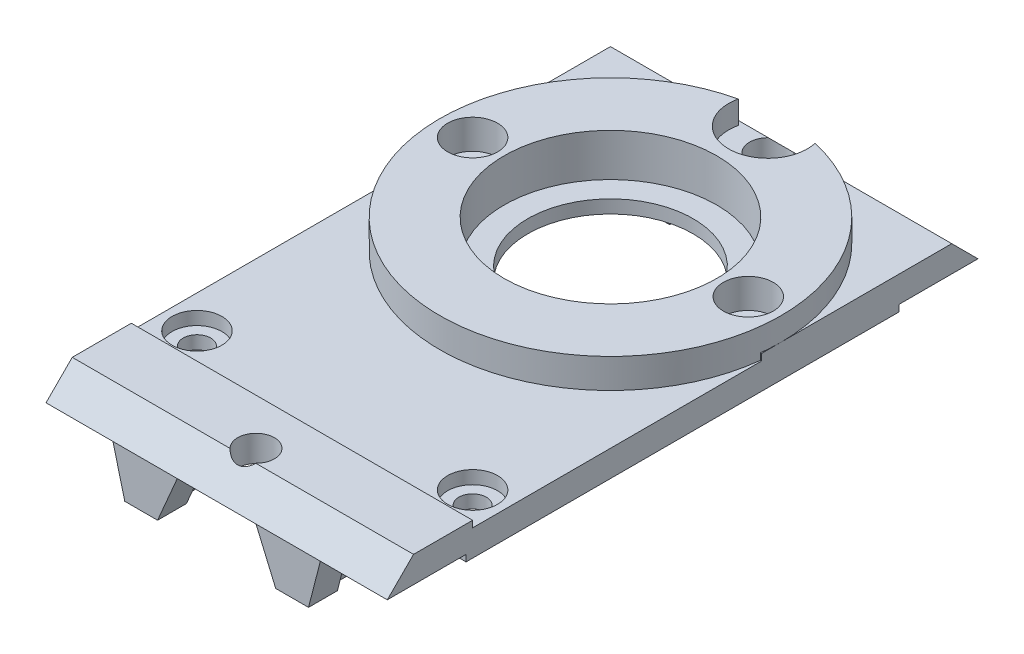
SolidWorks part; units mm, degrees
material "ABS"
ref_plane "正面" through (0, 0, 0) normal (0, 0, 1) x (1, 0, 0)
ref_plane "平面" through (0, 0, 0) normal (0, 1, 0) x (1, 0, 0)
ref_plane "右側面" through (0, 0, 0) normal (1, 0, 0) x (0, 0, -1)
sketch "ｽｹｯﾁ1" plane through (0, 0, 0) normal (0, 1, 0) x (1, 0, 0)
  line L0 (-13, 22.5) -> (13, 22.5)
  line L2 (-13, 22.5) -> (-13, -22.5)
  line L3 (-13, -22.5) -> (13, -22.5)
  line L4 (13, 22.5) -> (13, -22.5)
  line L5 (-13, 22.5) -> (13, -22.5) construction
  line L6 (-13, -22.5) -> (13, 22.5) construction
  point P7 (0, 0)
  dimension "D1" = 0
  dimension "D2" = 0
  dimension "D4" = 45
  dimension "D3" = 26
extrude "ﾎﾞｽ - 押し出し1" add sketch "ｽｹｯﾁ1" along normal blind 2
sketch "ｽｹｯﾁ4" plane through (0, 0, 22.5) normal (0, 0, 1) x (1, 0, 0)
  line L1 (-7, -3.5) -> (-4.5, -3.5)
  line L2 (-4.5, -3.5) -> (-3, 0)
  line L4 (3, 0) -> (4.5, -3.5)
  line L5 (4.5, -3.5) -> (7, -3.5)
  line L8 (7, -3.5) -> (7.9, 0)
  line L10 (-7, -3.5) -> (-7.9, 0)
  line L12 (3, 0) -> (0, 0) construction
  line L13 (0, 0) -> (-3, 0) construction
  line L14 (-7.9, 0) -> (-3, 0)
  line L15 (3, 0) -> (7.9, 0)
  line L16 (-13, 0) -> (13, 0) construction
  dimension "D1" = 7.9
  dimension "D2" = 0
  dimension "D3" = 3
  dimension "D5" = 2.5
  dimension "D6" = 7
  dimension "D9" = 3.5
extrude "ﾎﾞｽ - 押し出し3" add sketch "ｽｹｯﾁ4" against normal blind 6
sketch "ｽｹｯﾁ5" plane through (0, 2, 0) normal (0, 1, 0) x (1, 0, 0)
  line L1 (-13, -22.5) -> (13, -22.5) construction
  circle A0 centre (0, -19.5) radius 1.4
  dimension "D1" = 2.8
  dimension "D2" = 1.4
  dimension "D3" = 3
  dimension "D4" = 0
extrude "ｶｯﾄ - 押し出し1" cut sketch "ｽｹｯﾁ5" against normal up to next
fillet "ﾌｨﾚｯﾄ1" [suppressed] radius 2
sketch "ｽｹｯﾁ6" plane through (13, 0, 0) normal (1, 0, 0) x (0, 0, -1)
  line L1 (-16.5, 0) -> (16.5, 0)
  line L2 (-16.5, 0) -> (-16.5, -0.5)
  line L3 (-16.5, -0.5) -> (16.5, -0.5)
  line L4 (16.5, 0) -> (16.5, -0.5)
  line L5 (-16.5, 0) -> (16.5, -0.5) construction
  line L6 (-16.5, -0.5) -> (16.5, 0) construction
  point P4 (0, -0.25)
  dimension "D1" = 0.5
  dimension "D2" = 33
extrude "ﾎﾞｽ - 押し出し4" add sketch "ｽｹｯﾁ6" against normal up to surface (26 mm away) up to face at (-13, 1, 0)
sketch "ｽｹｯﾁ7" plane through (13, 0, 0) normal (1, 0, 0) x (0, 0, -1)
  line L0 (-22.5, 2) -> (22.5, 2) construction
  line L1 (-16, 2) -> (6, 2)
  line L2 (-16, 2) -> (-16, 1.5)
  line L3 (-16, 1.5) -> (6, 1.5)
  line L4 (6, 2) -> (6, 1.5)
  line L5 (-16, 2) -> (6, 1.5) construction
  line L6 (-16, 1.5) -> (6, 2) construction
  line L8 (-16.5, -3.5) -> (-16.5, -0.5) construction
  point P4 (-5, 1.75)
  dimension "D1" = 0.5
  dimension "D2" = 22
  dimension "D3" = 0.5
extrude "ｶｯﾄ - 押し出し2" cut sketch "ｽｹｯﾁ7" against normal up to next
hole_wizard "M2 丸平ねじ用座ぐり穴1" positions "ｽｹｯﾁ8" profile "ｽｹｯﾁ9" counterbore size "M2" standard "JIS" end condition through all
sketch "ｽｹｯﾁ8" plane through (0, 1.5, 0) normal (0, 1, 0) x (1, 0, 0)
  line L0 (7.7714, -16.5) -> (13, -16.5) construction
  point P0 (10.5, -13.5)
  dimension "D1" = 3
  dimension "D2" = 10.5
sketch "ｽｹｯﾁ9" plane through (10.5, 1.5, 13.5) normal (1, 0, 0) x (0, 0, 1)
  line L0 (0, 0) -> (0, 5)
  line L1 (0, 5) -> (1.05, 5)
  line L3 (1.05, 5) -> (1.05, 1)
  line L4 (1.05, 1) -> (1.9, 1)
  line L5 (1.9, 1) -> (1.9, 0)
  line L7 (1.9, 0) -> (0, 0)
  line L11 (0, -6.35) -> (0, 107.95) construction
  dimension "通し穴の直径" = 2.1
  dimension "通し穴の深さ" = 5
  dimension "座ぐり穴の直径" = 3.8
  dimension "座ぐり穴の深さ" = 1
chamfer "面取り1" distance 2 angle 45 2 edges at (0, 2, 22.5) (0, 2, -22.5)
mirror "ﾐﾗｰ1" about plane through (0, 0, 0) normal (0, 0, 1) of "ｶｯﾄ - 押し出し1", "ﾎﾞｽ - 押し出し3"
sketch "ｽｹｯﾁ11" plane through (0, 1.5, 0) normal (0, 1, 0) x (1, 0, 0)
  line L0 (0, -3.9875) -> (0, 3.9875) construction
  arc A0 (-2.925, 20.1667) -> (2.925, 20.1667) centre (0, 7.5) ccw
  circle A1 centre (10.5, -13.5) radius 1.05 construction
  arc A2 (-2.925, 20.1667) -> (2.925, 20.1667) centre (0, 19.5) ccw
  dimension "D1" = 26
  dimension "D2" = 21
  dimension "D3" = 6
extrude "ﾎﾞｽ - 押し出し5" add sketch "ｽｹｯﾁ11" along normal blind 2.25
hole_wizard "M2 丸平ねじ用座ぐり穴2" positions "ｽｹｯﾁ12" profile "ｽｹｯﾁ13" counterbore size "M2" standard "JIS" end condition through all
sketch "ｽｹｯﾁ12" plane through (0, 3.75, 0) normal (0, 1, 0) x (1, 0, 0)
  line L0 (10.5, -13.5) -> (10.5, 7.5) construction
  line L2 (13, -16) -> (13, 6) construction
  point P0 (10.5, 7.5)
  dimension "D1" = 21
sketch "ｽｹｯﾁ13" plane through (10.5, 3.75, -7.5) normal (1, 0, 0) x (0, 0, 1)
  line L0 (0, 0) -> (0, 7.25)
  line L1 (0, 7.25) -> (1.05, 7.25)
  line L3 (1.05, 7.25) -> (1.05, 2.25)
  line L4 (1.05, 2.25) -> (1.9, 2.25)
  line L5 (1.9, 2.25) -> (1.9, 0)
  line L7 (1.9, 0) -> (0, 0)
  line L11 (0, -6.35) -> (0, 107.95) construction
  dimension "通し穴の直径" = 2.1
  dimension "通し穴の深さ" = 7.25
  dimension "座ぐり穴の直径" = 3.8
  dimension "座ぐり穴の深さ" = 2.25
hole_wizard "M2 丸平ねじ用座ぐり穴3" positions "ｽｹｯﾁ15" profile "ｽｹｯﾁ16" counterbore size "M2" standard "JIS" end condition through all
sketch "ｽｹｯﾁ15" plane through (0, 3.75, 0) normal (0, 1, 0) x (1, 0, 0)
  point P0 (0, 7.5)
sketch "ｽｹｯﾁ16" plane through (0, 3.75, -7.5) normal (1, 0, 0) x (0, 0, 1)
  line L0 (0, 0) -> (0, 7.25)
  line L1 (0, 7.25) -> (6.3, 7.25)
  line L3 (6.3, 7.25) -> (6.3, 3.25)
  line L4 (6.3, 3.25) -> (8.1, 3.25)
  line L5 (8.1, 3.25) -> (8.1, 0)
  line L7 (8.1, 0) -> (0, 0)
  line L11 (0, -6.35) -> (0, 107.95) construction
  dimension "通し穴の直径" = 12.6
  dimension "通し穴の深さ" = 7.25
  dimension "座ぐり穴の直径" = 16.2
  dimension "座ぐり穴の深さ" = 3.25
mirror "ﾐﾗｰ2" about plane through (0, 0, 0) normal (1, 0, 0) of "M2 丸平ねじ用座ぐり穴1", "M2 丸平ねじ用座ぐり穴2"
ref_plane "平面1" through (0, 0, 19.5) normal (0, 0, 1) x (1, 0, 0)
sketch "ｽｹｯﾁ17" plane through (0, 0, 19.5) normal (0, 0, 1) x (1, 0, 0)
  line L0 (4.5, -3.5) -> (3, 0)
  line L1 (4.5, -3.5) -> (5.1, -3.5)
  line L2 (3, 0) -> (3.6, 0)
  line L3 (5.1, -3.5) -> (3.6, 0)
  line L4 (4.5, -3.5) -> (3.6, 0) construction
  line L5 (3, 0) -> (5.1, -3.5) construction
  line L6 (7.9, 0) -> (3, 0) construction
  line L7 (6.4, -3.5) -> (7, -3.5)
  line L8 (6.4, -3.5) -> (7.3, 0)
  line L9 (7, -3.5) -> (7.9, 0)
  line L10 (7.3, 0) -> (7.9, 0)
  line L11 (6.4, -3.5) -> (7.9, 0) construction
  line L12 (7, -3.5) -> (7.3, 0) construction
  line L13 (4.5, -3.5) -> (7, -3.5) construction
  point P5 (4.05, -1.75)
  point P14 (7.15, -1.75)
  dimension "D1" = 0.6
extrude "ｶｯﾄ - 押し出し3" cut sketch "ｽｹｯﾁ17" against normal mid plane 1.6
mirror "ﾐﾗｰ3" about plane through (0, 0, 0) normal (1, 0, 0) of "ｶｯﾄ - 押し出し3"
mirror "ﾐﾗｰ4" about plane through (0, 0, 0) normal (0, 0, 1) of "ﾐﾗｰ3", "ｶｯﾄ - 押し出し3"
